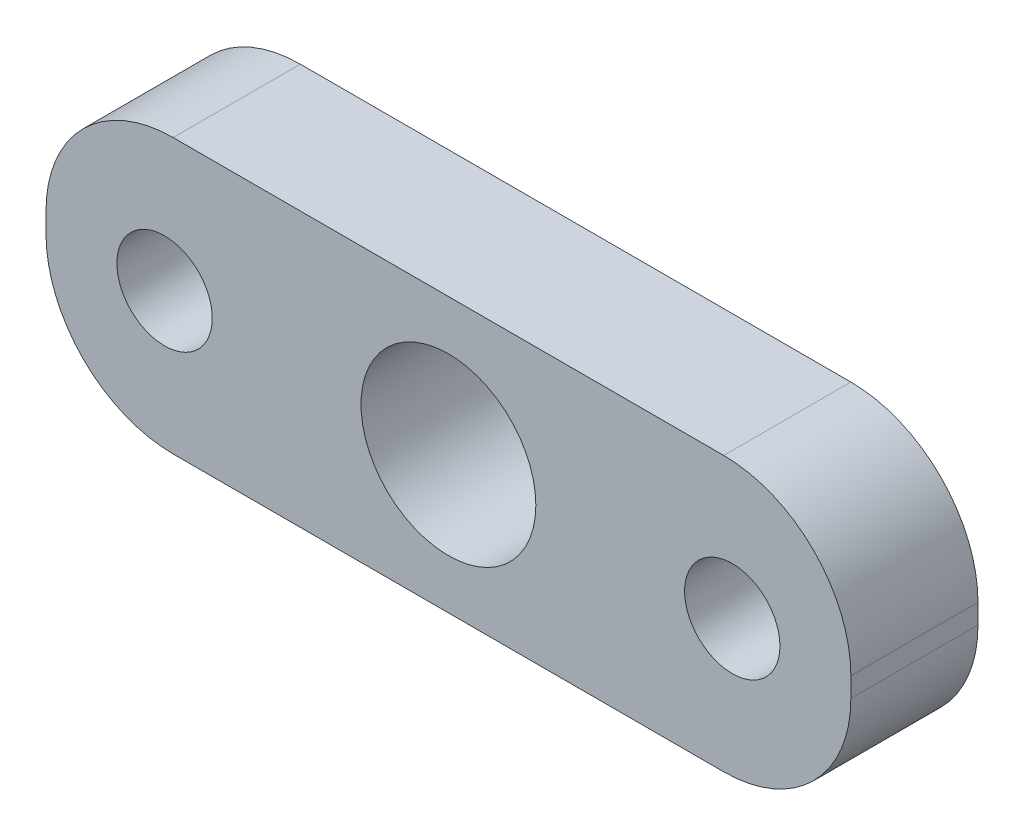
SolidWorks part; units mm, degrees
ref_plane "Front Plane" through (0, 0, 0) normal (0, 0, 1) x (1, 0, 0)
ref_plane "Top Plane" through (0, 0, 0) normal (0, 1, 0) x (1, 0, 0)
ref_plane "Right Plane" through (0, 0, 0) normal (1, 0, 0) x (0, 0, -1)
sketch "Sketch1" plane through (0, 0, 0) normal (0, 0, 1) x (1, 0, 0)
  line L0 (55, 0) -> (-55, 0) construction
  line L1 (12.66, -4.31) -> (-12.66, -4.31)
  line L2 (12.66, -4.31) -> (12.66, 4.31)
  line L3 (12.66, 4.31) -> (-12.66, 4.31)
  line L4 (-12.66, -4.31) -> (-12.66, 4.31)
  circle A0 centre (-8.93, 0) radius 1.5
  circle A1 centre (8.93, 0) radius 1.5
  circle A2 centre (0, 0) radius 2.75
  point P4 (12.66, 0)
  point P6 (0, 4.31)
  point P9 (0, 0)
  point P12 (0, 0)
  dimension "D1" = 3.73
  dimension "D3" = 17.86
  dimension "D2" = 3.73
extrude "Boss-Extrude1" add sketch "Sketch1" along normal blind 4
fillet "Fillet1" radius 4 4 edges at (12.66, -4.31, 2) (12.66, 4.31, 2) (-12.66, 4.31, 2) (-12.66, -4.31, 2)
